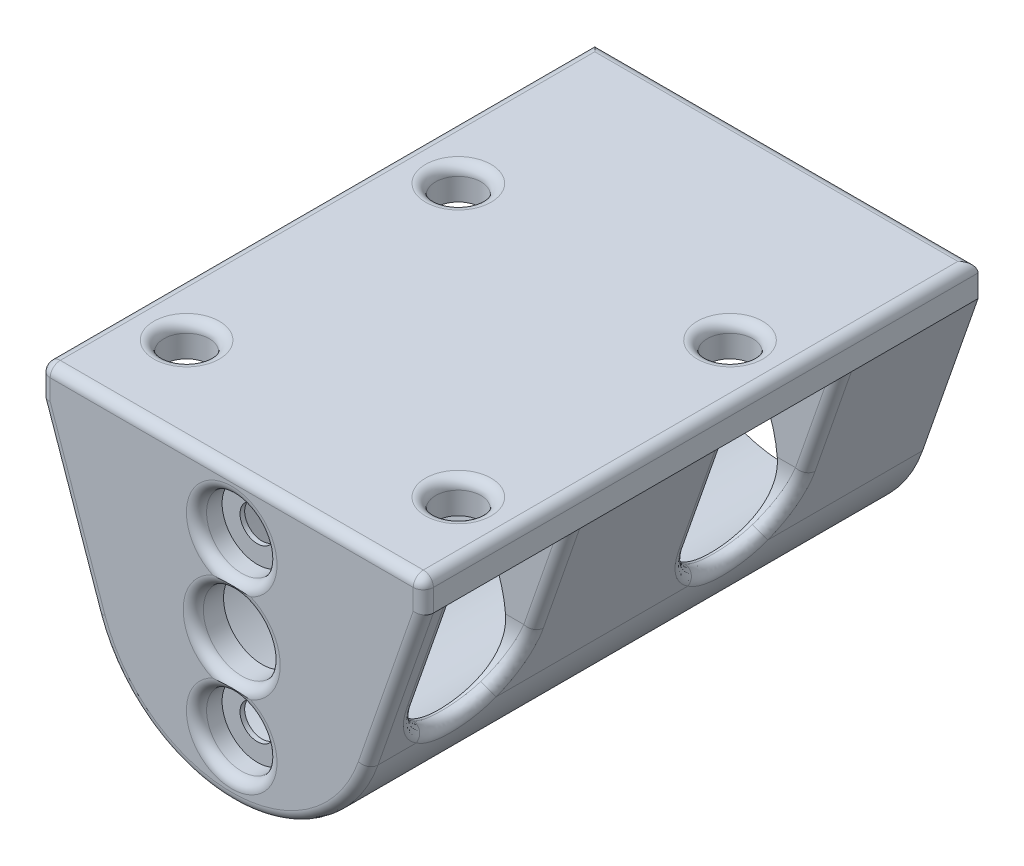
SolidWorks part; units mm, degrees
ref_plane "Front Plane" through (0, 0, 0) normal (0, 0, 1) x (1, 0, 0)
ref_plane "Top Plane" through (0, 0, 0) normal (0, 1, 0) x (1, 0, 0)
ref_plane "Right Plane" through (0, 0, 0) normal (1, 0, 0) x (0, 0, -1)
sketch "Sketch2" plane through (0, 0, 0) normal (0, 0, 1) x (1, 0, 0)
  circle A0 centre (0, 0) radius 12.7
  circle A1 centre (0, 0) radius 3.81
  circle A2 centre (0, 8.5) radius 1.7145
  circle A3 centre (0, -8.5) radius 1.7145
  dimension "D1" = 25.4
  dimension "D2" = 7.62
  dimension "D3" = 3.429
  dimension "D4" = 3.429
  dimension "D5" = 8.5
  dimension "D6" = 17
extrude "Boss-Extrude1" add sketch "Sketch2" along normal blind 3
sketch "Sketch3" plane through (0, 0, 3) normal (0, 0, 1) x (1, 0, 0)
  circle A0 centre (0, 8.5) radius 3.4925
  circle A1 centre (0, -8.5) radius 3.4925
  circle A2 centre (0, -8.5) radius 1.7145 construction
  circle A3 centre (0, 8.5) radius 1.7145 construction
  dimension "D1" = 6.985
extrude "Cut-Extrude1" cut sketch "Sketch3" against normal blind 2.54
sketch "Sketch4" plane through (0, 0, 3) normal (0, 0, 1) x (1, 0, 0)
  line L0 (-19, 14.3) -> (-19, 11.1)
  line L5 (19, 11.1) -> (13.5066, -4.6969)
  line L6 (19, 14.3) -> (-19, 14.3)
  line L7 (-19, 11.1) -> (-13.5066, -4.6969)
  line L9 (19, 11.1) -> (19, 14.3)
  circle A1 centre (0, 0) radius 12.7 construction
  arc A2 (-13.5066, -4.6969) -> (13.5066, -4.6969) centre (0, 0) ccw
  circle A4 centre (0, 0) radius 12.7
  point P24 (0, 14.3)
  dimension "D1" = 1.6
  dimension "D2" = 3.2
  dimension "D3" = 38
  dimension "D4" = 1.6
extrude "Boss-Extrude2" add sketch "Sketch4" against normal blind 55
ref_axis "Axis1" through (0, 0, 3) along (0, 0, -1)
sketch "Sketch7" plane through (0, 0, 3) normal (0, 0, 1) x (1, 0, 0)
  line L0 (11.1032, 11.1) -> (13.7063, 11.1) construction
  line L1 (13.7063, 11.1) -> (12.9387, 8.8927) construction
  line L3 (19, 14.3) -> (-19, 14.3) construction
  line L4 (-11.1032, 11.1) -> (-13.7063, 11.1) construction
  line L5 (-13.7063, 11.1) -> (-12.9387, 8.8927) construction
  line L6 (-19, 11.1) -> (-13.5066, -4.6969) construction
  line L9 (13.5066, -4.6969) -> (19, 11.1) construction
  arc A0 (-11.1032, 11.1) -> (-12.9387, 8.8927) centre (0, 0) ccw construction
  arc A1 (12.9387, 8.8927) -> (11.1032, 11.1) centre (0, 0) ccw construction
  circle A2 centre (4.4167, -4.1491) radius 0.3773
  dimension "D1" = 5
  dimension "D2" = 3.2
sketch "Sketch9" plane through (0, 0, 0) normal (1, 0, 0) x (0, 0, -1)
  line L1 (0, 11.1) -> (0, 1.1)
  line L4 (11.5, 11.1) -> (11.5, 1.1)
  line L6 (0, 11.1) -> (11.5, 11.1)
  line L7 (52, 11.1) -> (-3, 11.1) construction
  line L8 (0, -12.7) -> (0, 12.7) construction
  arc A0 (0, 1.1) -> (11.5, 1.1) centre (5.75, 1.1) ccw
  point P5 (5.75, 11.1)
  dimension "D2" = 10
  dimension "D3" = 10
  dimension "D1" = 11.5
extrude "Cut-Extrude4" cut sketch "Sketch9" against normal through all both and the other way through all
pattern_linear "Répétition linéaire1" count 2 spacing 26.9418 along (0, 0, -1) of "Cut-Extrude4"
hole_wizard "M4 Clearance Hole1" positions "Sketch10" profile "Sketch12" hole size "M4" standard "ANSI Metric"
sketch "Sketch10" plane through (0, 11.1, 0) normal (0, -1, 0) x (-1, 0, 0)
  line L2 (-13.4709, 6) -> (13.4709, 6)
  line L3 (-13.4709, 6) -> (-13.4709, 32.9418)
  line L4 (-13.4709, 32.9418) -> (13.4709, 32.9418)
  line L5 (13.4709, 6) -> (13.4709, 32.9418)
  line L6 (0, 6) -> (0, 32.9418) construction
  line L13 (0, 15.73) -> (0, -15.73) construction
  line L14 (19, -3) -> (13.5066, -3) construction
  point P0 (-13.4709, 6)
  point P2 (-13.4709, 32.9418)
  point P110 (13.4709, 32.9418)
  point P114 (13.4709, 6)
  dimension "D1" = 26.9418
  dimension "D2" = 9
  dimension "D3" = 26.9418
sketch "Sketch12" plane through (13.4709, 11.1, -6) normal (1, 0, 0) x (0, 0, -1)
  line L0 (0, 0) -> (0, 4.5519)
  line L1 (0, 4.5519) -> (2.25, 3.2)
  line L2 (2.25, 3.2) -> (2.25, 0)
  line L5 (2.25, 0) -> (0, 0)
  line L10 (0, 4.5519) -> (-2.25, 3.2) construction
  line L11 (0, -6.35) -> (0, 107.95) construction
  dimension "Hole Dia." = 4.5
  dimension "Hole Depth" = 3.2
  dimension "Drill Angle" = 118
extrude "Cut-Extrude6" cut sketch "Sketch7" against normal through all
sketch "Sketch17" plane through (0, 14.3, 0) normal (0, 1, 0) x (1, 0, 0)
  line L0 (19, -3) -> (19, 6)
  line L2 (19, -3) -> (-19, -3) construction
  line L3 (10, -3) -> (19, -3)
  line L4 (19, 6) -> (13.4709, 6) construction
  line L5 (-10, -3) -> (-19, -3)
  line L6 (-19, -3) -> (-19, 6)
  line L8 (-19, 52) -> (-19, -3) construction
  line L9 (19, 52) -> (19, -3) construction
  arc A0 (19, 6) -> (10, -3) centre (10, 6) cw
  arc A2 (-19, 6) -> (-10, -3) centre (-10, 6) ccw
extrude "Cut-Extrude8" [suppressed] cut sketch "Sketch17" against normal through all both and the other way through all
sketch "Sketch21" plane through (0, 0, 3) normal (0, 0, 1) x (1, 0, 0)
  circle A0 centre (4.4167, -4.1491) radius 0.3773 construction
  circle A1 centre (4.4167, -4.1491) radius 0.3773
extrude "Boss-Extrude4" add sketch "Sketch21" against normal up to surface (3 mm away) up to face at (4.794, -4.1491, 0)
fillet "Fillet1" radius 1 9 edges at (16.2533, 3.2015, 3) (0, -14.3, 3) (-16.2533, 3.2015, 3) (-19, 12.7, 3) (0, 14.3, 3) (19, 12.7, 3) (3.81, 0, 3) (3.4925, -8.5, 3) (3.4925, 8.5, 3)
fillet "Fillet2" radius 1 21 edges at (18.7071, 14.0071, 2.7071) (-18.7071, 14.0071, 2.7071) (17.2613, 6.1, 0) (13.5229, -4.65, -5.75) (17.2613, 6.1, -38.4418) (13.5229, -4.65, -32.6918) (-17.2613, 6.1, -26.9418) (-13.5229, -4.65, -32.6918) (-17.2613, 6.1, 0) (-13.5229, -4.65, -5.75) (0, 14.3, -52) (19, 14.3, -25) (-19, 14.3, -25) (-13.4709, 14.3, -8.25) (-13.4709, 14.3, -35.1918) (13.4709, 14.3, -35.1918) (13.4709, 14.3, -8.25) (17.2613, 6.1, -11.5) (17.2613, 6.1, -26.9418) (-17.2613, 6.1, -38.4418) (-17.2613, 6.1, -11.5)
fillet "Fillet3" radius 1 4 edges at (6.1709, 11.1, -32.6918) (6.1709, 11.1, -5.75) (-6.1709, 11.1, -5.75) (-6.1709, 11.1, -32.6918)
